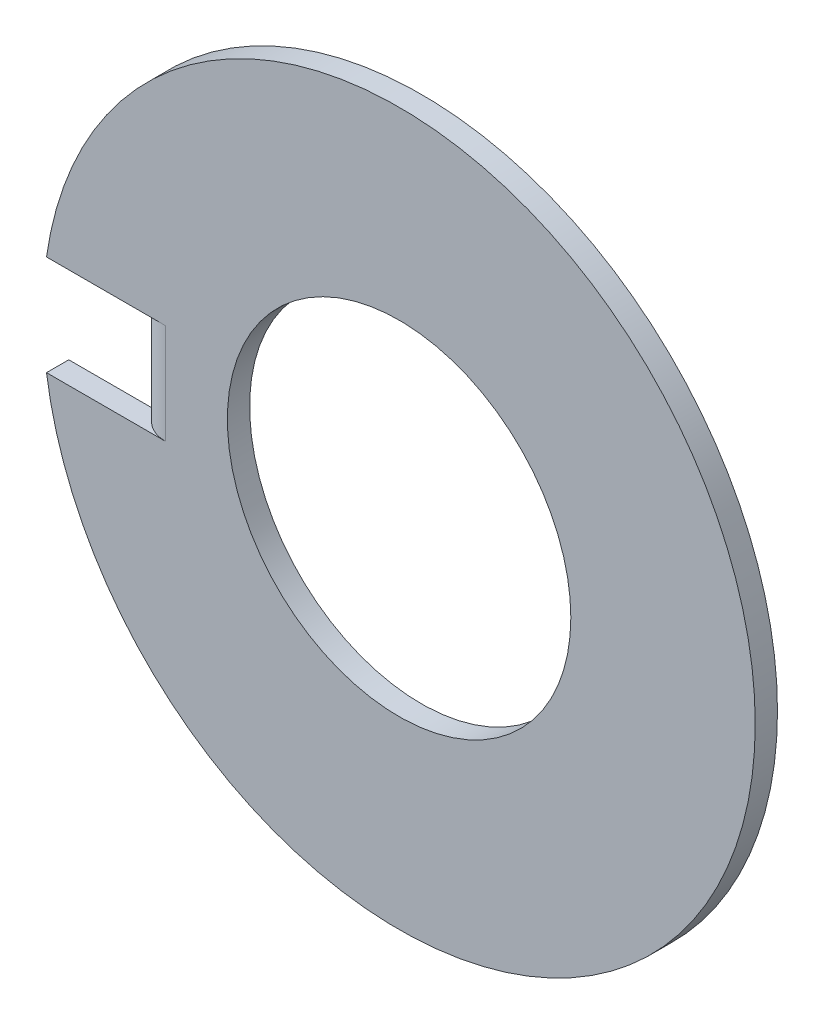
SolidWorks part; units mm, degrees
note: The reader was unsure of these and kept them because the rebuilt part matched: flange length of "Edge-Flange1".
ref_plane "Front" through (0, 0, 0) normal (0, 0, 1) x (1, 0, 0)
ref_plane "Top" through (0, 0, 0) normal (0, 1, 0) x (1, 0, 0)
ref_plane "Right" through (0, 0, 0) normal (1, 0, 0) x (0, 0, -1)
other "Configuration Table"
sketch "Sketch1" plane through (0, 0, 0) normal (0, 0, 1) x (1, 0, 0)
  line L0 (-15.841, 2.25) -> (-12, 2.25)
  line L1 (-12, 2.25) -> (-12, -2.25)
  line L2 (-12, -2.25) -> (-15.841, -2.25)
  arc A0 (-15.841, -2.25) -> (-15.841, 2.25) centre (0, 0) ccw
  circle A1 centre (0, 0) radius 7.715
  dimension "D2" = 2.25
sheet metal parameters "Sheet-Metal1" parameters "D1"=0.7366, "S"=1
base flange "Base-Flange1" sketch "Sketch1" reverse thickness direction yes parameters "D1"=0.7366
edge flange "Edge-Flange1" sketch "Sketch6" flange angle 90 flange length 3 flange position material inside bend radius 0.5 parameters "D6"=10
sketch "Sketch6" plane through (-12, 0, 0) normal (-1, 0, 0) x (0, 1, 0)
  line L2 (-2.25, 0) -> (-2.25, 3)
  line L3 (-2.25, 3) -> (2.25, 3)
  line L4 (2.25, 3) -> (2.25, 0)
  line L5 (2.25, 0) -> (-2.25, 0) construction
  line L6 (2.25, 0) -> (-2.25, 0)
bend "EdgeBend1" bend radius 0.5 bend angle 90 parameters "D5"=1
flat pattern "Flat-Pattern1" [suppressed]
sketch "Bend-Lines1" plane through (0, 0, 0) normal (0, 1, 0) x (-1, 0, 0)
bend of the flat pattern "Flatten-<EdgeBend1>1"
equation "\"D2@Sketch1\" = \"B@Sketch1\" / 2"
equation "\"D7@Edge-Flange1\"=\"D@Sketch1\" / 2-\"L@Sketch1\" - \"S@Sheet-Metal1\""
